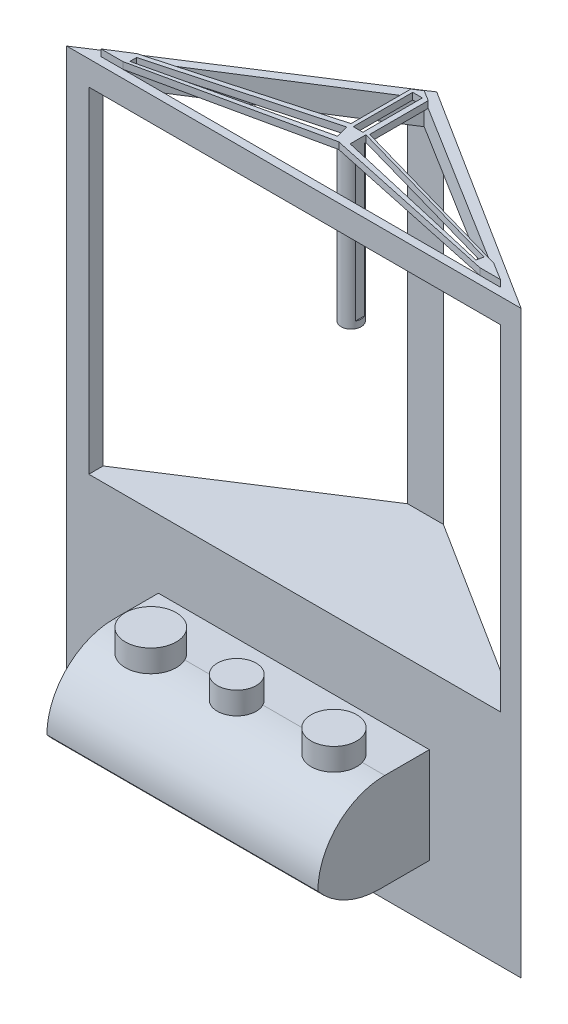
SolidWorks part; units mm, degrees
ref_plane "Front Plane" through (0, 0, 0) normal (0, 0, 1) x (1, 0, 0)
ref_plane "Top Plane" through (0, 0, 0) normal (0, 1, 0) x (1, 0, 0)
ref_plane "Right Plane" through (0, 0, 0) normal (1, 0, 0) x (0, 0, -1)
sketch "Sketch1" plane through (0, 0, 0) normal (0, 1, 0) x (1, 0, 0)
  line L0 (0, 0) -> (50.3954, 32.5622)
  line L1 (50.3954, 32.5622) -> (101.872, 0)
  line L2 (101.872, 0) -> (0, 0)
extrude "Boss-Extrude2" add sketch "Sketch1" along normal blind 130
sketch "Sketch5" plane through (0, 0, 0) normal (0, 0, 1) x (1, 0, 0)
  line L7 (0, 0) -> (101.872, 0)
  line L8 (101.872, 0) -> (101.872, 130)
  line L9 (101.872, 130) -> (0, 130)
  line L10 (0, 130) -> (0, 0)
  line L11 (0, 0) -> (101.872, 0)
  line L12 (101.872, 0) -> (101.872, 130)
  line L14 (0, 130) -> (0, 0)
  dimension "D1" = 0
sketch "Sketch8" plane through (0, 0, 0) normal (0, 0, 1) x (1, 0, 0)
  line L4 (4.966, 124.5108) -> (4.966, 49.3482)
  line L5 (4.966, 49.3482) -> (97.2415, 49.3482)
  line L6 (97.2415, 49.3482) -> (97.2415, 124.5108)
  line L7 (97.2415, 124.5108) -> (4.966, 124.5108)
sketch "Sketch9" plane through (0, 130, 0) normal (0, 1, 0) x (1, 0, 0)
  line L0 (5.9357, 1.7836) -> (50.2668, 29.8879)
  line L1 (50.2668, 29.8879) -> (95.4344, 1.7836)
  line L2 (95.4344, 1.7836) -> (5.9357, 1.7836)
extrude "Cut-Extrude2" cut sketch "Sketch9" against normal blind 20
extrude "Cut-Extrude3" cut sketch "Sketch8" against normal blind 30
sketch "Sketch10" plane through (0, 0, 0) normal (0, 0, 1) x (1, 0, 0)
  line L4 (20.564, 34.0493) -> (81.308, 34.0493)
  line L5 (20.564, 34.0493) -> (20.564, 12.5358)
  line L6 (20.564, 12.5358) -> (81.308, 12.5358)
  line L7 (81.308, 34.0493) -> (81.308, 12.5358)
  line L8 (20.564, 34.0493) -> (81.308, 12.5358) construction
  line L9 (20.564, 12.5358) -> (81.308, 34.0493) construction
  point P6 (50.936, 23.2925)
extrude "Boss-Extrude3" add sketch "Sketch10" along normal blind 25
fillet "Fillet1" radius 15 1 edges at (50.936, 34.0493, 25)
fillet "Fillet2" radius 18 1 edges at (50.936, 12.5358, 25)
sketch "Sketch13" plane through (0, 34.0493, 0) normal (0, 1, 0) x (1, 0, 0)
  circle A0 centre (31.3321, -12.4717) radius 5.6969
extrude "Boss-Extrude4" add sketch "Sketch13" along normal blind 5
sketch "Sketch14" plane through (0, 34.0493, 0) normal (0, 1, 0) x (1, 0, 0)
  circle A0 centre (71.3777, -11.4664) radius 5.1042
extrude "Boss-Extrude5" add sketch "Sketch14" along normal blind 5
sketch "Sketch15" plane through (0, 34.0493, 0) normal (0, 1, 0) x (1, 0, 0)
  circle A0 centre (50.0982, -11.969) radius 4.3564
extrude "Boss-Extrude6" add sketch "Sketch15" along normal blind 5
sketch "Sketch16" plane through (0, 130, 0) normal (0, 1, 0) x (1, 0, 0)
  line L0 (50.438, 30) -> (50.685, 1.7836) construction
  line L1 (46.43, 30) -> (54.446, 30) construction
  line L2 (5.9357, 1.7836) -> (95.4344, 1.7836) construction
  line L3 (10.8487, 4.8983) -> (50.5615, 15.8918)
  line L4 (50.2668, 29.8879) -> (5.9357, 1.7836) construction
  line L5 (50.5615, 15.8918) -> (50.6096, 10.3951)
  line L6 (50.6096, 10.3951) -> (10.8487, 1.7836)
  line L7 (10.8487, 1.7836) -> (5.9357, 1.7836)
  line L8 (5.9357, 1.7836) -> (10.8487, 4.8983)
extrude "Boss-Extrude7" add sketch "Sketch16" along normal blind 1.5 separate body
sketch "Sketch17" plane through (0, 130, 0) normal (0, 1, 0) x (1, 0, 0)
  line L0 (91.5505, 4.2003) -> (50.5615, 15.8918)
  line L1 (95.4344, 1.7836) -> (50.2668, 29.8879) construction
  line L2 (50.5615, 15.8918) -> (50.6096, 10.3951)
  line L3 (50.6096, 10.3951) -> (90.8612, 1.7836)
  line L4 (5.9357, 1.7836) -> (95.4344, 1.7836) construction
  line L5 (90.8612, 1.7836) -> (95.4344, 1.7836)
  line L6 (95.4344, 1.7836) -> (91.5505, 4.2003)
extrude "Boss-Extrude8" add sketch "Sketch17" along normal blind 1.5
sketch "Sketch18" plane through (0, 130, 0) normal (0, 1, 0) x (1, 0, 0)
  line L0 (48.4353, 28.7268) -> (48.4353, 15.3032)
  line L1 (50.2668, 29.8879) -> (5.9357, 1.7836) construction
  line L2 (50.5615, 15.8918) -> (10.8487, 4.8983) construction
  line L3 (48.4353, 15.3032) -> (50.5615, 15.8918)
  line L4 (50.5615, 15.8918) -> (52.625, 15.3032)
  line L5 (91.5505, 4.2003) -> (50.5615, 15.8918) construction
  line L6 (52.625, 15.3032) -> (52.625, 28.4206)
  line L7 (95.4344, 1.7836) -> (50.2668, 29.8879) construction
  line L8 (52.625, 28.4206) -> (50.2668, 29.8879)
  line L9 (50.2668, 29.8879) -> (48.4353, 28.7268)
extrude "Boss-Extrude9" add sketch "Sketch18" along normal blind 1.5
sketch "Sketch19" plane through (0, 130, 0) normal (0, -1, 0) x (1, 0, 0)
  circle A0 centre (50.2658, -13.4993) radius 2.2542
extrude "Boss-Extrude10" add sketch "Sketch19" along normal blind 35
sketch "Sketch20" plane through (0, 130, 0) normal (0, -1, 0) x (-1, 0, 0)
  line L0 (-11.5666, 4.1101) -> (-48.624, 14.1633)
  line L2 (-48.624, 14.1633) -> (-49.3877, 11.3482)
  line L3 (-49.3877, 11.3482) -> (-11.5666, 2.599)
  line L4 (-11.5666, 2.599) -> (-11.5666, 4.1101)
extrude "Cut-Extrude4" cut sketch "Sketch20" against normal through all
sketch "Sketch21" plane through (0, 131.5, 0) normal (0, 1, 0) x (1, 0, 0)
  line L0 (52.2658, 14.8141) -> (52.2658, 11.2852)
  line L1 (52.2658, 11.2852) -> (88.9111, 2.8336)
  line L2 (88.9111, 2.8336) -> (89.2551, 4.3253)
  line L3 (89.2551, 4.3253) -> (52.2658, 14.8141)
  point P2 (0, 0)
  point P5 (0, 0)
  point P6 (52.2658, 14.8141)
extrude "Cut-Extrude7" cut sketch "Sketch21" against normal blind 35
sketch "Sketch23" plane through (0, 131.5, 0) normal (0, 1, 0) x (1, 0, 0)
  line L0 (49.274, 28.2924) -> (49.274, 14.9606)
  line L1 (49.274, 14.9606) -> (51.4459, 14.9606)
  line L2 (51.4459, 14.9606) -> (51.4459, 28.2924)
  line L3 (51.4459, 28.2924) -> (49.274, 28.2924)
extrude "Cut-Extrude9" cut sketch "Sketch23" against normal blind 36
